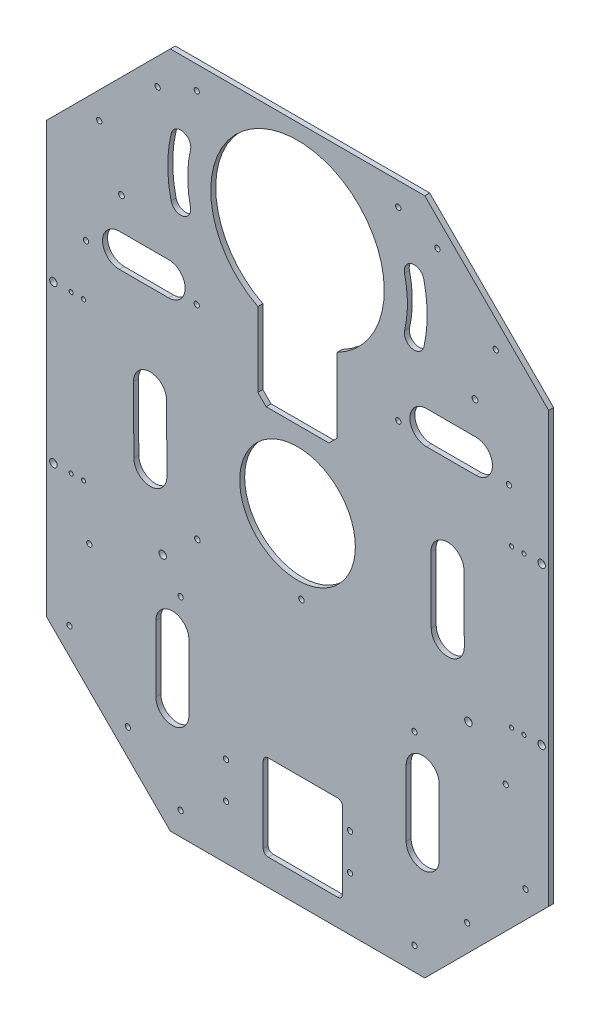
SolidWorks part; units mm, degrees
ref_plane "前视基准面" through (0, 0, 0) normal (0, 0, 1) x (1, 0, 0)
ref_plane "上视基准面" through (0, 0, 0) normal (0, 1, 0) x (1, 0, 0)
ref_plane "右视基准面" through (0, 0, 0) normal (1, 0, 0) x (0, 0, -1)
sketch "草图1" plane through (0, 0, 0) normal (0, 0, 1) x (1, 0, 0)
  line L0 (-125.8249, 164.7138) -> (-125.8249, 174.7138)
  line L1 (-115.8249, 174.7138) -> (168.6751, 174.7138)
  line L2 (-125.8249, 164.7138) -> (-125.8249, -65.2862)
  line L3 (-116.3249, -75.2862) -> (168.1751, -75.2862)
  line L4 (178.1751, 164.7138) -> (178.1751, -65.2862)
  line L5 (-125.8249, 174.7138) -> (-115.8249, 174.7138)
  line L6 (168.6751, 174.7138) -> (178.1751, 174.7138)
  line L7 (178.1751, 174.7138) -> (178.1751, 164.7138)
  line L8 (178.1751, -65.2862) -> (178.1751, -75.2862)
  line L9 (178.1751, -75.2862) -> (168.1751, -75.2862)
  line L10 (-116.3249, -75.2862) -> (-125.8249, -75.2862)
  line L11 (-125.8249, -75.2862) -> (-125.8249, -65.2862)
  point P8 (178.1751, -75.2862)
  point P11 (178.1751, 174.7138)
  point P14 (-125.8249, 174.7138)
  dimension "D1" = 304
  dimension "D2" = 250
extrude "凸台-拉伸1" add sketch "草图1" along normal blind 3
sketch "草图2" plane through (0, 0, 3) normal (0, 0, 1) x (1, 0, 0)
  circle A4 centre (173.9251, 93.6305) radius 2.25 construction
  circle A5 centre (173.9251, -1.3695) radius 2.25 construction
  circle A6 centre (-121.5749, 93.6305) radius 2.25 construction
  circle A7 centre (-121.5749, -1.3695) radius 2.25 construction
  circle A8 centre (173.9251, 93.6305) radius 2.25
  circle A9 centre (173.9251, -1.3695) radius 2.25
  circle A10 centre (-121.5749, 93.6305) radius 2.25
  circle A11 centre (-121.5749, -1.3695) radius 2.25
extrude "切除-拉伸1" cut sketch "草图2" against normal up to next
sketch "草图3" plane through (0, 0, 3) normal (0, 0, 1) x (1, 0, 0)
  circle A3 centre (155.6751, 93.6305) radius 1.25 construction
  circle A4 centre (163.1751, 93.6305) radius 1.25 construction
  circle A5 centre (155.6751, 93.6305) radius 1.25
  circle A6 centre (163.1751, 93.6305) radius 1.25
  circle A7 centre (163.1751, -1.3695) radius 1.25 construction
  circle A8 centre (155.6751, -1.3695) radius 1.25 construction
  circle A9 centre (163.1751, -1.3695) radius 1.25
  circle A10 centre (155.6751, -1.3695) radius 1.25
  circle A11 centre (-103.3249, 93.6305) radius 1.25 construction
  circle A12 centre (-110.8249, 93.6305) radius 1.25 construction
  circle A13 centre (-103.3249, -1.3695) radius 1.25 construction
  circle A14 centre (-110.8249, -1.3695) radius 1.25 construction
  circle A15 centre (-103.3249, 93.6305) radius 1.25
  circle A16 centre (-110.8249, 93.6305) radius 1.25
  circle A17 centre (-103.3249, -1.3695) radius 1.25
  circle A18 centre (-110.8249, -1.3695) radius 1.25
extrude "切除-拉伸2" cut sketch "草图3" against normal up to next
ref_plane "基准面1" through (26.4251, 0, 0) normal (-1, 0, 0) x (0, 0, 1)
sketch "草图6" plane through (0, 0, 3) normal (0, 0, 1) x (1, 0, 0)
  line L0 (-120.8249, -105.2862) -> (173.6751, -105.2862)
  line L18 (-125.8249, -75.2862) -> (-125.8249, -100.2862)
  line L21 (178.1751, -100.2862) -> (178.1751, -75.2862)
  line L22 (178.1751, -75.2862) -> (-125.8249, -75.2862)
  line L23 (178.1751, 174.7138) -> (178.1751, 199.7138)
  line L24 (173.6751, 229.7138) -> (-120.8249, 229.7138)
  line L25 (-125.8249, 174.7138) -> (-125.8249, 199.7138)
  line L26 (178.1751, 174.7138) -> (-125.8249, 174.7138) construction
  line L27 (-125.8249, 174.7138) -> (178.1751, 174.7138)
  line L28 (-125.8249, 199.7138) -> (-125.8249, 229.7138)
  line L29 (-125.8249, 229.7138) -> (-120.8249, 229.7138)
  line L30 (173.6751, 229.7138) -> (178.1751, 229.7138)
  line L31 (178.1751, 229.7138) -> (178.1751, 199.7138)
  line L32 (178.1751, -100.2862) -> (178.1751, -105.2862)
  line L33 (178.1751, -105.2862) -> (173.6751, -105.2862)
  line L34 (-125.8249, -100.2862) -> (-125.8249, -105.2862)
  line L35 (-125.8249, -105.2862) -> (-120.8249, -105.2862)
  point P16 (178.1751, -105.2862)
  point P21 (-125.8249, 229.7138)
  dimension "D1" = 55
  dimension "D2" = 30
extrude "凸台-拉伸2" add sketch "草图6" against normal blind 3
sketch "草图7" plane through (0, 0, 3) normal (0, 0, 1) x (1, 0, 0)
  line L0 (178.1751, 229.7138) -> (-125.8249, 229.7138) construction
  line L1 (-125.8249, 229.7138) -> (-125.8249, -105.2862) construction
  line L2 (-125.8249, -105.2862) -> (178.1751, -105.2862) construction
  circle A0 centre (-112.0749, 219.7138) radius 2.1
  circle A1 centre (-112.0749, -95.2862) radius 2.1
  dimension "D1" = 10
  dimension "D2" = 13.75
  dimension "D3" = 13.75
  dimension "D4" = 10
  dimension "D5" = 4.2
  dimension "D6" = 4.2
extrude "切除-拉伸4" cut sketch "草图7" against normal up to next
mirror "镜向3" about plane through (26.4251, 0, 0) normal (-1, 0, 0) of "切除-拉伸4"
fillet "圆角1" radius 5 4 edges at (-125.8249, -105.2862, 1.5) (178.1751, -105.2862, 1.5) (178.1751, 229.7138, 1.5) (-125.8249, 229.7138, 1.5)
sketch "草图17" plane through (0, 0, 3) normal (0, 0, 1) x (1, 0, 0)
  line L2 (173.1751, 229.7138) -> (-120.8249, 229.7138) construction
  circle A2 centre (-80.3893, 159.7138) radius 1.75
  circle A3 centre (133.6107, 159.7138) radius 1.75
  dimension "D1" = 70
  dimension "D2" = 70
  dimension "D3" = 3.5
  dimension "D4" = 3.5
extrude "切除-拉伸13" cut sketch "草图17" against normal blind 10
sketch "草图20" plane through (0, 0, 3) normal (0, 0, 1) x (1, 0, 0)
  circle A11 centre (-55.4429, -16.2862) radius 2.25
  circle A12 centre (-34.4429, 2.2138) radius 1.65
  circle A13 centre (28.5571, 2.2138) radius 1.65
  circle A14 centre (129.5571, -11.2862) radius 2.25
  circle A15 centre (28.5571, -39.7862) radius 1.65
  circle A16 centre (-34.4429, -39.7862) radius 1.65
  circle A17 centre (39.5571, -79.2862) radius 2.25
  circle A18 centre (6.95, -78.7685) radius 1.8
  circle A19 centre (-55.4429, -79.2862) radius 1.8
  circle A20 centre (-25.05, -78.7685) radius 1.8
  dimension "D21" = 4.5
  dimension "D22" = 3.3
  dimension "D23" = 3.3
  dimension "D24" = 3.3
  dimension "D25" = 3.3
  dimension "D26" = 4.5
  dimension "D27" = 4.5
  dimension "D28" = 3.6
  dimension "D29" = 3.6
  dimension "D30" = 3.6
extrude "切除-拉伸15" cut sketch "草图20" against normal up to next
sketch "Sketch1" plane through (0, 0, 3) normal (0, 0, 1) x (1, 0, 0)
  line L0 (2.1751, 142.5705) -> (50.1751, 142.5705) construction
  line L2 (2.1751, 142.5705) -> (2.1751, 97.5705)
  line L3 (7.1751, 92.5705) -> (45.1751, 92.5705)
  line L4 (50.1751, 142.5705) -> (50.1751, 97.5705)
  line L5 (45.1751, 92.5705) -> (50.1751, 97.5705)
  line L6 (2.1751, 97.5705) -> (7.1751, 92.5705)
  line L7 (-134.5175, -63.0882) -> (186.8676, 155.3492) construction
  line L8 (186.8676, -63.0882) -> (-134.5175, 155.3492) construction
  arc A0 (50.1751, 142.5705) -> (2.1751, 142.5705) centre (26.1751, 189.2636) ccw
  circle A2 centre (26.1751, 46.1305) radius 35
  point P7 (50.1751, 92.5705)
  point P8 (2.1751, 92.5705)
  dimension "D1" = 105
  dimension "D2" = 70
  dimension "D3" = 50
  dimension "D4" = 48
extrude "Cut-Extrude1" cut sketch "Sketch1" against normal blind 10
sketch "Sketch2" plane through (0, 0, 3) normal (0, 0, 1) x (1, 0, 0)
  line L0 (-125.8249, 224.7138) -> (-125.8249, -100.2862) construction
  line L1 (-125.8249, 207.2369) -> (-23.1525, 207.2369)
  line L2 (-125.8249, 207.2369) -> (-125.8249, 251.1305)
  line L3 (-125.8249, 251.1305) -> (178.1751, 251.1305)
  line L4 (178.1751, 207.2369) -> (178.1751, 251.1305)
  line L5 (-125.8249, -98.8695) -> (-125.8249, 191.1305) construction
  line L6 (-125.8249, -27.1706) -> (178.1751, -27.1706)
  line L7 (-125.8249, -27.1706) -> (-125.8249, -158.8695)
  line L8 (-125.8249, -158.8695) -> (178.1751, -158.8695)
  line L9 (178.1751, -27.1706) -> (178.1751, -158.8695)
  line L10 (178.1751, -100.2862) -> (178.1751, 224.7138) construction
  line L11 (-115.8249, 201.1305) -> (168.1751, 201.1305) construction
  line L12 (168.1751, -108.8695) -> (-115.8249, -108.8695) construction
  line L13 (75.5026, 207.2369) -> (178.1751, 207.2369)
  arc A0 (-7.2919, 229.7138) -> (2.1751, 142.5705) centre (26.1751, 189.2636) ccw construction
  arc A1 (75.5026, 207.2369) -> (-23.1525, 207.2369) centre (26.1751, 189.2636) ccw
  arc A2 (50.1751, 142.5705) -> (59.642, 229.7138) centre (26.1751, 189.2636) ccw construction
  dimension "D1" = 50
  dimension "D2" = 50
extrude "Extrude1" add sketch "Sketch2" against normal up to vertex (3 mm away) up to point (-125.8249, -100.2862, 0)
sketch "Sketch3" plane through (0, 0, 3) normal (0, 0, 1) x (1, 0, 0)
  line L0 (-125.8249, 176.1305) -> (-50.8249, 251.1305)
  line L1 (-125.8249, 251.1305) -> (-125.8249, -158.8695) construction
  line L2 (178.1751, 251.1305) -> (-125.8249, 251.1305) construction
  line L3 (-50.8249, 251.1305) -> (103.1751, 251.1305)
  line L4 (103.1751, 251.1305) -> (178.1751, 176.1305)
  line L5 (178.1751, -158.8695) -> (178.1751, 251.1305) construction
  line L6 (178.1751, 176.1305) -> (178.1751, 299.6027)
  line L7 (178.1751, 299.6027) -> (-125.8249, 299.6027)
  line L8 (-125.8249, 299.6027) -> (-125.8249, 176.1305)
  line L9 (-125.8249, -83.8695) -> (-50.8249, -158.8695)
  line L10 (-125.8249, -158.8695) -> (178.1751, -158.8695) construction
  line L11 (-50.8249, -158.8695) -> (103.1751, -158.8695)
  line L12 (103.1751, -158.8695) -> (178.1751, -83.8695)
  line L13 (178.1751, -83.8695) -> (178.1751, -212.4712)
  line L14 (178.1751, -212.4712) -> (-125.8249, -212.4712)
  line L15 (-125.8249, -212.4712) -> (-125.8249, -83.8695)
  dimension "D1" = 45
  dimension "D2" = 45
  dimension "D3" = 45
  dimension "D4" = 75
  dimension "D5" = 75
  dimension "D6" = 75
  dimension "D7" = 75
extrude "Cut-Extrude2" cut sketch "Sketch3" against normal blind 10 contours L8 L0 L3 L4 L6 L7 | L15 L9 L11 L12 L13 L14
sketch "Sketch5" plane through (0, 0, 0) normal (0, 0, -1) x (-1, 0, 0)
  line L0 (59.5749, -52.8695) -> (59.5749, -92.8695) construction
  line L1 (39.5749, -92.8695) -> (39.5749, -52.8695) construction
  line L2 (-111.9251, -52.8695) -> (-111.9251, -92.8695) construction
  line L3 (-91.9251, -92.8695) -> (-91.9251, -52.8695) construction
  line L8 (59.5749, -52.8695) -> (59.5749, -92.8695)
  line L9 (39.5749, -92.8695) -> (39.5749, -52.8695)
  line L10 (-111.9251, -52.8695) -> (-111.9251, -92.8695)
  line L11 (-91.9251, -92.8695) -> (-91.9251, -52.8695)
  line L12 (51.8249, 120.1222) -> (81.8249, 120.1222)
  line L13 (81.8249, 140.1222) -> (51.8249, 140.1222)
  line L14 (-104.1641, 120.1222) -> (-134.1641, 120.1222)
  line L15 (-134.1641, 140.1222) -> (-104.1641, 140.1222)
  arc A0 (59.5749, -52.8695) -> (39.5749, -52.8695) centre (49.5749, -52.8695) ccw construction
  arc A1 (39.5749, -92.8695) -> (59.5749, -92.8695) centre (49.5749, -92.8695) ccw construction
  arc A2 (-111.9251, -92.8695) -> (-91.9251, -92.8695) centre (-101.9251, -92.8695) ccw construction
  arc A3 (-91.9251, -52.8695) -> (-111.9251, -52.8695) centre (-101.9251, -52.8695) ccw construction
  arc A16 (59.5749, -52.8695) -> (39.5749, -52.8695) centre (49.5749, -52.8695) ccw
  arc A17 (39.5749, -92.8695) -> (59.5749, -92.8695) centre (49.5749, -92.8695) ccw
  arc A18 (-111.9251, -92.8695) -> (-91.9251, -92.8695) centre (-101.9251, -92.8695) ccw
  arc A19 (-91.9251, -52.8695) -> (-111.9251, -52.8695) centre (-101.9251, -52.8695) ccw
  arc A20 (81.8249, 120.1222) -> (81.8249, 140.1222) centre (81.8249, 130.1222) ccw
  arc A21 (51.8249, 140.1222) -> (51.8249, 120.1222) centre (51.8249, 130.1222) ccw
  arc A22 (-104.1641, 120.1222) -> (-104.1641, 140.1222) centre (-104.1641, 130.1222) ccw
  arc A23 (-134.1641, 140.1222) -> (-134.1641, 120.1222) centre (-134.1641, 130.1222) ccw
  arc A24 (-102.6889, 171.717) -> (-90.9925, 174.3993) centre (-96.8407, 173.0582) ccw
  arc A25 (-90.9297, 204.3993) -> (-90.9925, 174.3993) centre (-26.1751, 189.2636) ccw
  arc A26 (-102.6147, 207.1305) -> (-102.6889, 171.717) centre (-26.1751, 189.2636) ccw
  arc A27 (-90.9297, 204.3993) -> (-102.6147, 207.1305) centre (-96.7722, 205.7649) ccw
  arc A28 (38.6424, 174.3993) -> (50.3388, 171.717) centre (44.4985, 173.0926) ccw
  arc A29 (38.6424, 174.3993) -> (38.5796, 204.3993) centre (-27.9554, 189.2599) ccw
  arc A30 (50.2646, 207.1305) -> (38.5796, 204.3993) centre (44.4301, 205.7305) ccw
  arc A31 (50.3388, 171.717) -> (50.2646, 207.1305) centre (-24.1776, 189.2678) ccw
  arc A32 (-90.9297, 204.3993) -> (-90.9925, 174.3993) centre (-26.1751, 189.2636) ccw construction
extrude "Cut-Extrude3" cut sketch "Sketch5" against normal blind 3
sketch "Sketch6" plane through (0, 0, 0) normal (0, 0, -1) x (-1, 0, 0)
  circle A0 centre (-87.1751, 125.1305) radius 1.6 construction
  circle A1 centre (-154.1751, 125.1305) radius 1.6 construction
  circle A2 centre (-146.1751, 191.9966) radius 1.6 construction
  circle A3 centre (-110.8197, 227.3519) radius 1.6 construction
  circle A4 centre (-87.1751, 237.1305) radius 1.6 construction
  circle A5 centre (-87.1751, 125.1305) radius 1.6
  circle A6 centre (-154.1751, 125.1305) radius 1.6
  circle A7 centre (-146.1751, 191.9966) radius 1.6
  circle A8 centre (-110.8197, 227.3519) radius 1.6
  circle A9 centre (-87.1751, 237.1305) radius 1.6
  circle A10 centre (101.8249, 125.1305) radius 1.6 construction
  circle A11 centre (34.8249, 125.1305) radius 1.6 construction
  circle A12 centre (93.8249, 191.9966) radius 1.6 construction
  circle A13 centre (58.4696, 227.3519) radius 1.6 construction
  circle A14 centre (34.8249, 237.1305) radius 1.6 construction
  circle A15 centre (101.8249, 125.1305) radius 1.6
  circle A16 centre (34.8249, 125.1305) radius 1.6
  circle A17 centre (93.8249, 191.9966) radius 1.6
  circle A18 centre (58.4696, 227.3519) radius 1.6
  circle A19 centre (34.8249, 237.1305) radius 1.6
  circle A20 centre (99.8249, -32.8695) radius 1.6 construction
  circle A21 centre (44.5749, -32.8695) radius 1.6 construction
  circle A22 centre (111.8249, -81.7356) radius 1.6 construction
  circle A23 centre (76.4696, -117.0909) radius 1.6 construction
  circle A24 centre (44.5749, -144.8695) radius 1.6 construction
  circle A25 centre (-96.9251, -144.8695) radius 1.6 construction
  circle A26 centre (-128.8197, -117.0909) radius 1.6 construction
  circle A27 centre (-164.1751, -81.7356) radius 1.6 construction
  circle A28 centre (-96.9251, -32.8695) radius 1.6 construction
  circle A29 centre (-152.1751, -32.8695) radius 1.6 construction
  circle A30 centre (99.8249, -32.8695) radius 1.6
  circle A31 centre (44.5749, -32.8695) radius 1.6
  circle A32 centre (111.8249, -81.7356) radius 1.6
  circle A33 centre (76.4696, -117.0909) radius 1.6
  circle A34 centre (44.5749, -144.8695) radius 1.6
  circle A35 centre (-96.9251, -144.8695) radius 1.6
  circle A36 centre (-128.8197, -117.0909) radius 1.6
  circle A37 centre (-164.1751, -81.7356) radius 1.6
  circle A38 centre (-96.9251, -32.8695) radius 1.6
  circle A39 centre (-152.1751, -32.8695) radius 1.6
extrude "Cut-Extrude4" cut sketch "Sketch6" against normal blind 5
sketch "Sketch7" plane through (0, 0, 0) normal (0, 0, -1) x (-1, 0, 0)
  line L0 (-12.4251, -137.8695) -> (-46.4251, -137.8695) construction
  line L1 (-50.4251, -90.8695) -> (-8.4251, -90.8695)
  line L2 (-53.4251, -93.8695) -> (-53.4251, -139.8695)
  line L3 (-50.4251, -142.8695) -> (-8.4251, -142.8695)
  line L4 (-5.4251, -93.8695) -> (-5.4251, -139.8695)
  line L5 (-48.4251, -135.8695) -> (-48.4251, -128.8695) construction
  line L6 (-10.4251, -128.8695) -> (-10.4251, -135.8695) construction
  line L7 (-15.4251, -120.8695) -> (-16.9251, -120.8695) construction
  arc A0 (-8.4251, -142.8695) -> (-5.4251, -139.8695) centre (-8.4251, -139.8695) ccw
  arc A1 (-53.4251, -139.8695) -> (-50.4251, -142.8695) centre (-50.4251, -139.8695) ccw
  arc A2 (-8.4251, -90.8695) -> (-5.4251, -93.8695) centre (-8.4251, -93.8695) cw
  arc A3 (-50.4251, -90.8695) -> (-53.4251, -93.8695) centre (-50.4251, -93.8695) ccw
  circle A4 centre (-57.9251, -104.3695) radius 1.6
  circle A5 centre (-57.9251, -126.3695) radius 1.6
  circle A6 centre (17.0749, -126.3695) radius 1.6
  circle A7 centre (17.0749, -104.3695) radius 1.6
  dimension "D5" = 3
  dimension "D6" = 3.2
  dimension "D1" = 5
  dimension "D2" = 5
  dimension "D3" = 5
  dimension "D4" = 30
extrude "Cut-Extrude5" cut sketch "Sketch7" against normal blind 5
sketch "Sketch8" plane through (0, 0, 0) normal (0, 0, -1) x (-1, 0, 0)
  line L0 (-116.9421, 66.5035) -> (-117.108, 26.5038) construction
  line L1 (-106.9422, 66.462) -> (-107.1081, 26.4624)
  line L2 (-126.942, 66.545) -> (-127.1079, 26.5453)
  line L3 (-26.1751, 251.1305) -> (-27.8751, -158.8695) construction
  line L4 (-27.0251, 46.1305) -> (-117.0251, 46.5037) construction
  line L5 (63.0579, 65.7572) -> (62.892, 25.7575) construction
  line L6 (-103.1751, 251.1305) -> (50.8249, 251.1305) construction
  line L7 (53.058, 65.7986) -> (52.8921, 25.799)
  line L8 (73.0578, 65.7157) -> (72.8919, 25.716)
  arc A0 (-106.9422, 66.462) -> (-126.942, 66.545) centre (-116.9421, 66.5035) ccw
  arc A1 (-127.1079, 26.5453) -> (-107.1081, 26.4624) centre (-117.108, 26.5038) ccw
  arc A2 (53.058, 65.7986) -> (73.0578, 65.7157) centre (63.0579, 65.7572) cw
  arc A3 (72.8919, 25.716) -> (52.8921, 25.799) centre (62.892, 25.7575) cw
  point P2 (-117.0251, 46.5037)
  point P17 (62.9749, 45.7573)
  dimension "D1" = 10
  dimension "D2" = 40
  dimension "D3" = 90
extrude "Cut-Extrude6" cut sketch "Sketch8" against normal blind 5
